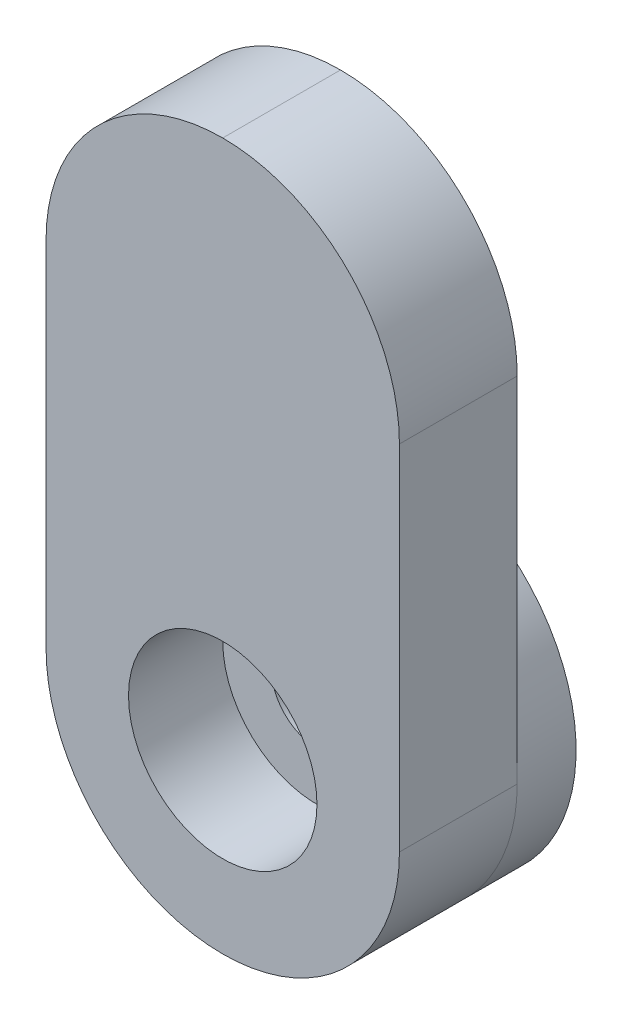
SolidWorks part; units mm, degrees
ref_plane "Front Plane" through (0, 0, 0) normal (0, 0, 1) x (1, 0, 0)
ref_plane "Top Plane" through (0, 0, 0) normal (0, 1, 0) x (1, 0, 0)
ref_plane "Right Plane" through (0, 0, 0) normal (1, 0, 0) x (0, 0, -1)
sketch "Sketch1" plane through (0, 0, 0) normal (0, 0, 1) x (1, 0, 0)
  line L1 (-9.525, 38.1) -> (9.525, 38.1)
  line L2 (-9.525, 38.1) -> (-9.525, 0)
  line L3 (-9.525, 0) -> (9.525, 0)
  line L4 (9.525, 38.1) -> (9.525, 0)
  line L5 (-9.525, 38.1) -> (9.525, 0) construction
  line L6 (-9.525, 0) -> (9.525, 38.1) construction
  point P0 (0, 19.05)
  dimension "D1" = 19.05
  dimension "D2" = 38.1
extrude "Boss-Extrude1" add sketch "Sketch1" along normal blind 6.35
hole_wizard "CBORE for #8 Socket Head Cap Screw1" positions "Sketch2" profile "Sketch3" counterbore size "#8" standard "ANSI Inch" end condition through all
sketch "Sketch2" plane through (0, 0, 6.35) normal (0, 0, 1) x (1, 0, 0)
  line L0 (-9.525, 0) -> (9.525, 0) construction
  point P0 (0, 9.525)
  dimension "D1" = 9.525
sketch "Sketch3" plane through (0, 9.525, 6.35) normal (1, 0, 0) x (0, -1, 0)
  line L0 (0, 0) -> (0, 6.35)
  line L1 (0, 6.35) -> (2.4575, 6.35)
  line L3 (2.4575, 6.35) -> (2.4574, 5.08)
  line L4 (2.4574, 5.08) -> (5.08, 5.08)
  line L5 (5.08, 5.08) -> (5.08, 0)
  line L7 (5.08, 0) -> (0, 0)
  line L11 (0, -6.35) -> (0, 107.95) construction
  dimension "Thru Hole Dia." = 4.9149
  dimension "Thru Hole Depth" = 6.35
  dimension "C'Bore Dia." = 10.16
  dimension "C'Bore Depth" = 5.08
sketch "Sketch4" plane through (0, 0, 0) normal (0, 0, -1) x (-1, 0, 0)
  circle A0 centre (0, 9.525) radius 2.4575
  circle A1 centre (0, 9.525) radius 9.525
  circle A2 centre (0, 9.525) radius 2.4574 construction
  dimension "D1" = 19.05
extrude "Boss-Extrude2" add sketch "Sketch4" along normal blind 3.175
sketch "Sketch5" plane through (0, 0, -3.175) normal (0, 0, -1) x (-1, 0, 0)
  line L0 (-3.6422, 14.7266) -> (-1.4095, 11.538)
  line L1 (1.4095, 11.538) -> (3.6422, 14.7266)
  line L2 (0, 11.9825) -> (0, 15.875) construction
  line L3 (0, 9.525) -> (-1.4095, 11.538) construction
  line L4 (0, 9.525) -> (1.4095, 11.538) construction
  arc A0 (3.6422, 14.7266) -> (-3.6422, 14.7266) centre (0, 9.525) ccw
  arc A1 (1.4095, 11.538) -> (-1.4095, 11.538) centre (0, 9.525) ccw
  circle A2 centre (0, 9.525) radius 2.4575 construction
  dimension "D1" = 12.7
  dimension "D2" = 35
extrude "Boss-Extrude3" add sketch "Sketch5" along normal blind 2.54
fillet "Fillet1" radius 9.525 4 edges at (9.525, 38.1, 3.175) (-9.525, 38.1, 3.175) (9.525, 0, 3.175) (-9.525, 0, 3.175)
